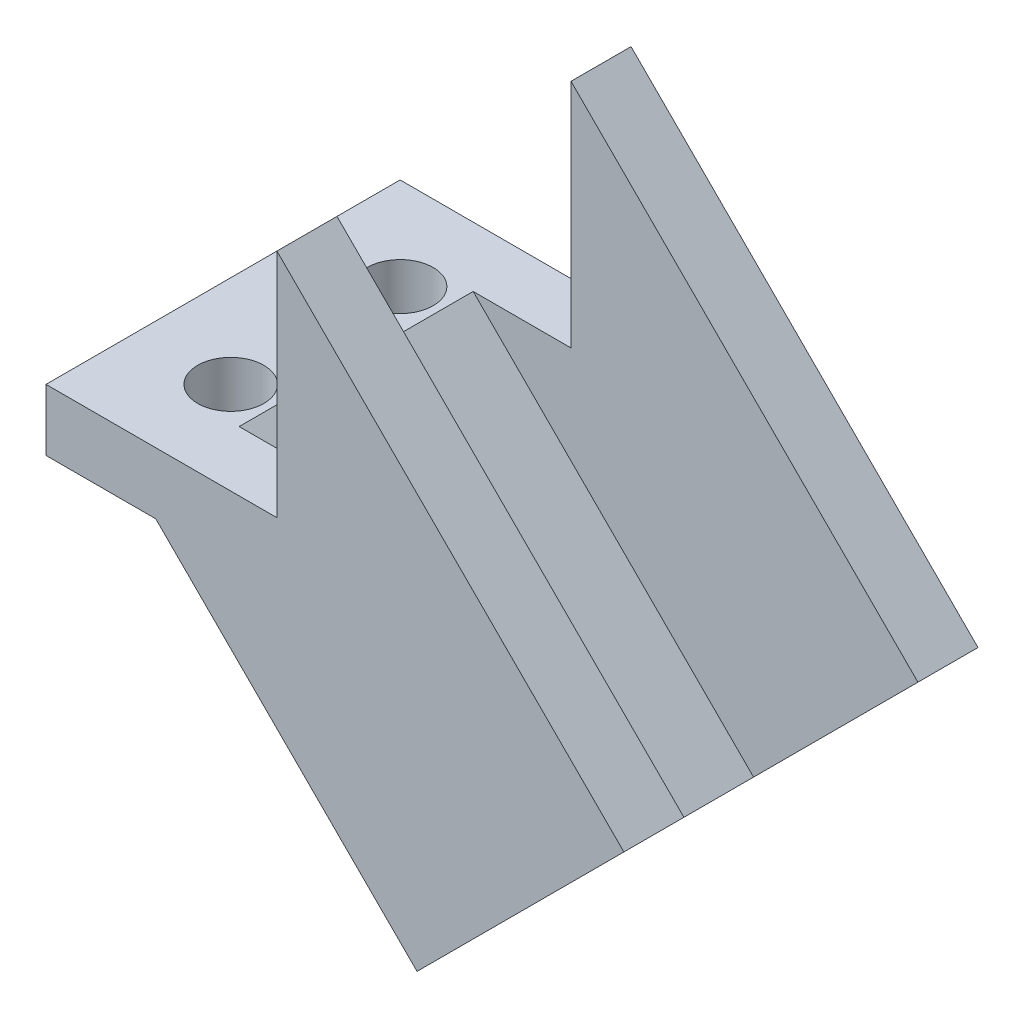
SolidWorks part; units mm, degrees
ref_plane "前视基准面" through (0, 0, 0) normal (0, 0, 1) x (1, 0, 0)
ref_plane "上视基准面" through (0, 0, 0) normal (0, 1, 0) x (1, 0, 0)
ref_plane "右视基准面" through (0, 0, 0) normal (1, 0, 0) x (0, 0, -1)
sketch "草图1" plane through (0, 0, 0) normal (0, 0, 1) x (1, 0, 0)
  line L0 (-23, 312.8277) -> (-23, 297.8277)
  line L1 (-23, 297.8277) -> (-38, 297.8277)
  line L2 (-38, 297.8277) -> (-38, 293.8277)
  line L3 (-38, 422.2397) -> (-38, 15) construction
  line L4 (-38, 293.8277) -> (-30.8701, 293.8277)
  line L5 (-29.2132, 297.8277) -> (81.2311, 187.3833) construction
  line L7 (-11.0711, 279.6855) -> (-0.4645, 290.2921)
  line L9 (-0.4645, 290.2921) -> (-23, 312.8277)
  line L13 (-23, 312.8277) -> (91.8377, 197.9899) construction
  line L14 (-11.0711, 279.6855) -> (-13.8995, 276.8571)
  line L15 (-13.8995, 276.8571) -> (-30.8701, 293.8277)
  dimension "D1" = 4
extrude "凸台-拉伸1" add sketch "草图1" along normal blind 4 and the other way blind 19
sketch "草图2" plane through (-145.3783, 145.3783, 0) normal (0.7071, -0.7071, 0) x (0, 0, -1)
  line L0 (-79, 205.061) -> (209, 205.061) construction
  line L1 (-0.1, 205.061) -> (15.1, 205.061)
  line L2 (-0.1, 205.061) -> (-0.1, 189.8391)
  line L3 (-0.1, 189.8391) -> (15.1, 189.8391)
  line L4 (15.1, 205.061) -> (15.1, 189.8391)
  line L5 (-4, 185.9391) -> (-4, 204.9391) construction
  line L6 (19, 185.9391) -> (19, 204.9391) construction
  line L7 (19, 204.9391) -> (-4, 204.9391) construction
  dimension "D1" = 3.9
  dimension "D2" = 3.9
  dimension "D3" = 15.1
extrude "切除-拉伸1" cut sketch "草图2" against normal blind 67
sketch "草图3" plane through (0, 293.8277, 0) normal (0, -1, 0) x (1, 0, 0)
  line L0 (-38, 4) -> (-30.8701, 4) construction
  line L1 (-38, -19) -> (-30.8701, -19) construction
  line L2 (-38, -19) -> (-38, 4) construction
  circle A0 centre (-32, -2) radius 2.15
  circle A1 centre (-32, -13) radius 2.15
  dimension "D1" = 6
  dimension "D2" = 6
  dimension "D3" = 4.3
  dimension "D4" = 4.3
  dimension "D5" = 6
  dimension "D6" = 6
extrude "切除-拉伸2" cut sketch "草图3" against normal blind 67 and the other way blind 67
sketch "草图4" plane through (0, 293.8277, 0) normal (0, -1, 0) x (1, 0, 0)
  circle A0 centre (-32, -2) radius 4
  circle A1 centre (-32, -13) radius 4
  dimension "D1" = 8
  dimension "D2" = 8
extrude "切除-拉伸3" cut sketch "草图4" along normal blind 67
sketch "草图5" plane through (131.4788, 131.4788, 0) normal (-0.7071, -0.7071, 0) x (0, 0, 1)
  line L0 (4, 229.596) -> (4, 205.596) construction
  line L1 (-19, 205.596) -> (4, 205.596) construction
  circle A0 centre (-7.5, 213.596) radius 2.15
  dimension "D1" = 4.3
  dimension "D2" = 11.5
  dimension "D3" = 8
extrude "切除-拉伸4" cut sketch "草图5" against normal blind 67
